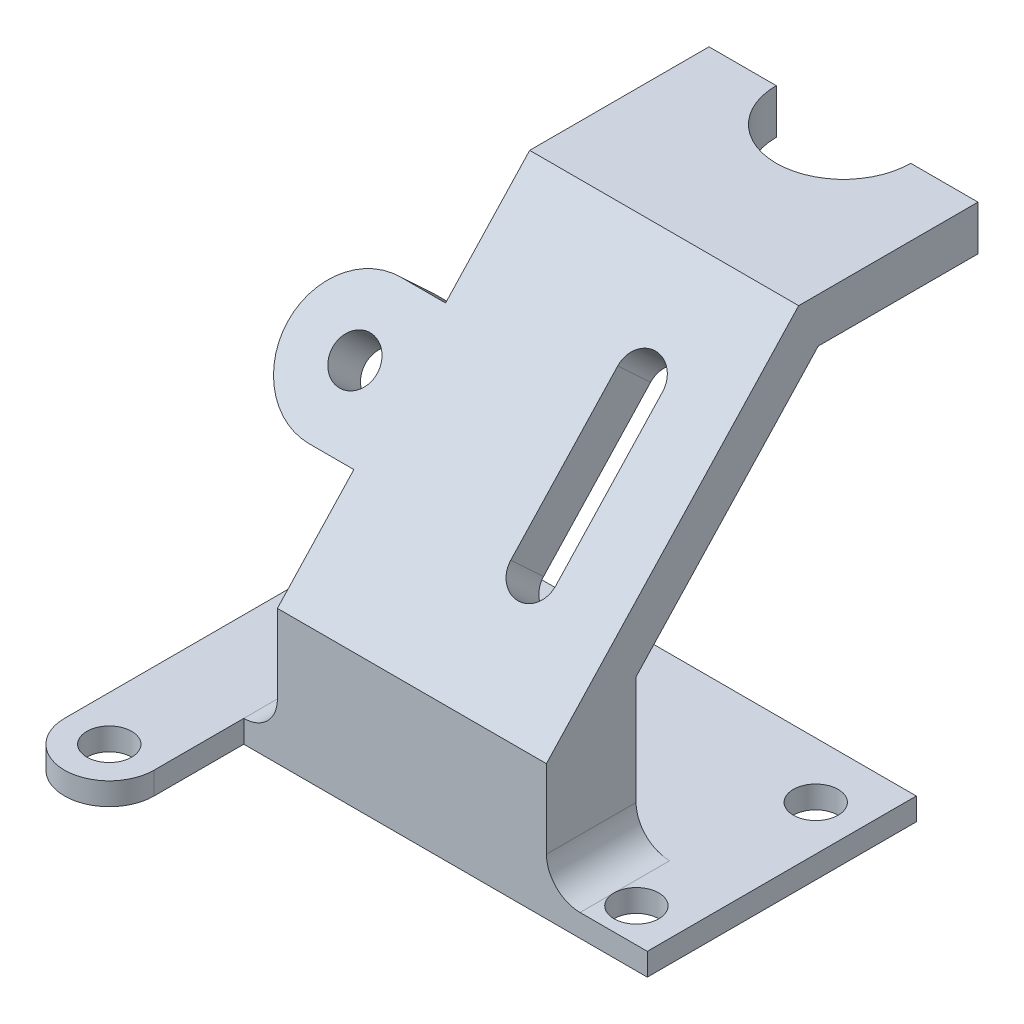
SolidWorks part; units mm, degrees
ref_plane "Front Plane" through (0, 0, 0) normal (0, 0, 1) x (1, 0, 0)
ref_plane "Top Plane" through (0, 0, 0) normal (0, 1, 0) x (1, 0, 0)
ref_plane "Right Plane" through (0, 0, 0) normal (1, 0, 0) x (0, 0, -1)
sketch "Sketch1" plane through (0, 0, 0) normal (0, 0, 1) x (1, 0, 0)
  line L0 (-16.6915, 0) -> (25.7767, 0)
  line L1 (25.7767, 0) -> (25.7767, 2)
  line L2 (25.7767, 2) -> (19.7767, 2)
  line L6 (-18.2233, 0) -> (-16.6915, 0)
  line L7 (-18.2233, 0) -> (-18.2233, 2)
  line L8 (-18.2233, 2) -> (-10.2233, 2)
  line L9 (-7.2233, 5) -> (-7.2233, 12)
  line L10 (-7.2233, 12) -> (16.7767, 12)
  line L11 (16.7767, 12) -> (16.7767, 5)
  line L12 (-7.2233, 2) -> (16.7767, 2)
  line L13 (-10.2233, 2) -> (19.7767, 2)
  arc A0 (-10.2233, 2) -> (-7.2233, 5) centre (-10.2233, 5) ccw
  arc A1 (16.7767, 5) -> (19.7767, 2) centre (19.7767, 5) ccw
  dimension "D7" = 3
  dimension "D8" = 3
  dimension "D1" = 44
  dimension "D2" = 8
  dimension "D3" = 24
  dimension "D4" = 2
  dimension "D5" = 2
  dimension "D6" = 10
extrude "Boss-Extrude1" add sketch "Sketch1" against normal blind 24 contours L12 L8 L7 L6 L0 L1 L2 region at (3.7767, 1, 0)
extrude "Boss-Extrude2" add sketch "Sketch1<4>" against normal blind 8 contours A1 L11 L10 L9 A0 L13 L12 region at (4.7767, 6.9314, 0)
sketch "Sketch1<4>" plane through (0, 0, 0) normal (0, 0, 1) x (1, 0, 0) same geometry as "Sketch1"
sketch "Sketch2" plane through (0, 2, 0) normal (0, 1, 0) x (1, 0, 0)
  line L0 (-18.2233, 0) -> (-10.2233, 0)
  line L1 (-10.2233, 0) -> (-10.2233, -8)
  line L2 (-18.2233, 0) -> (-18.2233, -8)
  arc A0 (-18.2233, -8) -> (-10.2233, -8) centre (-14.2233, -8) ccw
  circle A1 centre (-14.2233, -8) radius 2
  dimension "D1" = 8
  dimension "D3" = 4
  dimension "D2" = 8
extrude "Boss-Extrude3" add sketch "Sketch2" against normal blind 2
sketch "Sketch3" plane through (0, 2, 0) normal (0, 1, 0) x (1, 0, 0)
  line L0 (25.7767, 24) -> (25.7767, 0) construction
  line L1 (-18.2233, 24) -> (-18.2233, -8) construction
  circle A0 centre (21.7767, 3.0277) radius 2
  circle A1 centre (-14.2233, -8) radius 2 construction
  circle A2 centre (21.7767, 19.0277) radius 2
  circle A3 centre (-14.2233, 19.0277) radius 2
  dimension "D1" = 4
  dimension "D2" = 36
  dimension "D3" = 4
  dimension "D6" = 4
  dimension "D4" = 16
  dimension "D5" = 4
  dimension "D7" = 4
extrude "Cut-Extrude1" cut sketch "Sketch3" against normal through all
sketch "Sketch5" plane through (16.7767, 0, 0) normal (1, 0, 0) x (0, 0, -1)
  line L0 (8, 12) -> (0, 12)
  line L1 (0, 12) -> (22.5059, 36.1347)
  line L2 (8, 12) -> (8, 14.7138)
  line L3 (8, 14.7138) -> (19.2012, 26.7256)
  line L4 (8, 14.7138) -> (19.8095, 14.7138) construction
  line L5 (22.5059, 36.1347) -> (38.5059, 36.1347)
  line L6 (38.5059, 36.1347) -> (38.5059, 32.1347)
  line L7 (38.5059, 32.1347) -> (24.2452, 32.1347)
  line L8 (24.2452, 32.1347) -> (19.2012, 26.7256)
  point P4 (21.7232, 29.4302)
  dimension "D1" = 47
  dimension "D2" = 33
  dimension "D3" = 16
  dimension "D4" = 4
  dimension "D5" = 4
  dimension "D6" = 4
extrude "Boss-Extrude4" add sketch "Sketch5" against normal blind 24
sketch "Sketch6" plane through (0, 5.5815, 5.9854) normal (0, 0.682, 0.7314) x (1, 0, 0)
  line L0 (-7.2233, 18.7762) -> (-11.2233, 18.7762)
  line L1 (-7.2233, 41.7762) -> (-7.2233, 8.7762) construction
  line L2 (-7.2233, 30.7762) -> (-11.2233, 30.7762)
  line L3 (-7.2233, 41.7762) -> (16.7767, 41.7762) construction
  line L4 (-7.2233, 30.7762) -> (-7.2233, 18.7762)
  line L5 (8.7767, 32.7762) -> (8.7767, 18.7762) construction
  line L6 (10.7767, 32.7762) -> (10.7767, 18.7762)
  line L7 (6.7767, 32.7762) -> (6.7767, 18.7762)
  line L8 (16.7767, 41.7762) -> (16.7767, 8.7762) construction
  arc A0 (-11.2233, 18.7762) -> (-11.2233, 30.7762) centre (-11.2233, 24.7762) cw
  circle A1 centre (-11.2233, 24.7762) radius 2
  arc A2 (10.7767, 32.7762) -> (6.7767, 32.7762) centre (8.7767, 32.7762) ccw
  arc A3 (6.7767, 18.7762) -> (10.7767, 18.7762) centre (8.7767, 18.7762) ccw
  point P12 (8.7767, 25.7762)
  point P19 (0, 0)
  point P20 (0, 0)
  point P21 (0, 0)
  point P22 (0, 0)
  point P23 (0, 0)
  point P24 (0, 0)
  point P25 (0, 0)
  dimension "D2" = 6
  dimension "D3" = 4
  dimension "D6" = 2
  dimension "D1" = 4
  dimension "D4" = 17
  dimension "D5" = 8
  dimension "D7" = 9
  dimension "D8" = 14
extrude "Boss-Extrude5" add sketch "Sketch6" against normal blind 4
extrude "Cut-Extrude2" cut sketch "Sketch6<5>" against normal blind 4 contours L7 A3 L6 A2 region at (8.7767, 24.433, -11.594)
sketch "Sketch6<5>" plane through (0, 5.5815, 5.9854) normal (0, 0.682, 0.7314) x (1, 0, 0) same geometry as "Sketch6"
sketch "Sketch7" plane through (0, 36.1347, 0) normal (0, 1, 0) x (1, 0, 0)
  line L0 (-7.2233, 38.5059) -> (16.7767, 38.5059) construction
  line L1 (-1.2233, 38.5059) -> (10.7767, 38.5059)
  arc A0 (-1.2233, 38.5059) -> (10.7767, 38.5059) centre (4.7767, 38.5059) ccw
  dimension "D1" = 6
  dimension "D2" = 12
extrude "Cut-Extrude4" cut sketch "Sketch7" against normal through all
